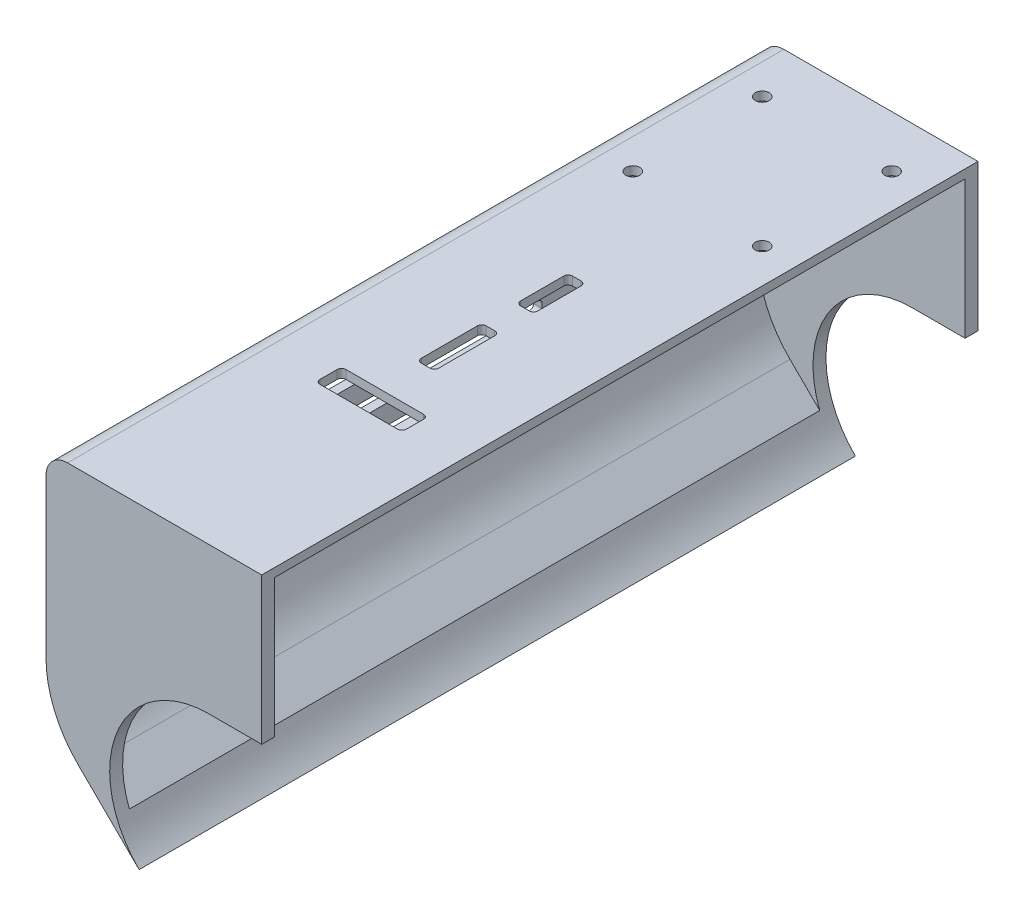
SolidWorks part; units mm, degrees
ref_plane "Front Plane" through (0, 0, 0) normal (0, 0, 1) x (1, 0, 0)
ref_plane "Top Plane" through (0, 0, 0) normal (0, 1, 0) x (1, 0, 0)
ref_plane "Right Plane" through (0, 0, 0) normal (1, 0, 0) x (0, 0, -1)
sketch "Sketch1" plane through (0, 0, 0) normal (0, 0, 1) x (1, 0, 0)
  line L0 (-176.4226, 3.6462) -> (-198.0073, 24.9918)
  line L1 (-198.0073, 24.9918) -> (-198.0073, 77)
  line L2 (-198.0073, 77) -> (-148.0073, 77)
  line L4 (-160.25, 43) -> (-148.0073, 43)
  line L6 (-148.0073, 43) -> (-148.0073, 77)
  arc A1 (-160.25, 43) -> (-176.4226, 3.6462) centre (-160.25, 20) ccw
extrude "Boss-Extrude1" add sketch "Sketch1" against normal blind 3
sketch "Sketch2" plane through (0, 0, -166) normal (0, 0, -1) x (-1, 0, 0)
  line L5 (198.0073, 24.9918) -> (198.0073, 77)
  line L6 (198.0073, 77) -> (148.0073, 77)
  line L7 (148.0073, 77) -> (148.0073, 43)
  line L8 (148.0073, 43) -> (160.25, 43)
  line L9 (176.4226, 3.6462) -> (198.0073, 24.9918)
  line L10 (198.0073, 24.9918) -> (198.0073, 77)
  line L11 (198.0073, 77) -> (148.0073, 77)
  line L12 (148.0073, 77) -> (148.0073, 43)
  line L13 (148.0073, 43) -> (160.25, 43)
  line L14 (176.4226, 3.6462) -> (198.0073, 24.9918)
  arc A1 (176.4226, 3.6462) -> (160.25, 43) centre (160.25, 20) ccw
  arc A2 (176.4226, 3.6462) -> (160.25, 43) centre (160.25, 20) ccw
  dimension "D1" = 0
extrude "Boss-Extrude2" add sketch "Sketch2" against normal blind 3 separate body
sketch "Sketch3" plane through (0, 0, -3) normal (0, 0, -1) x (-1, 0, 0)
  line L0 (181.6864, 11.6645) -> (196.0073, 25.8268)
  line L1 (196.0073, 25.8268) -> (196.0073, 75)
  line L2 (196.0073, 75) -> (148.0073, 75)
  line L3 (148.0073, 77) -> (148.0073, 75)
  line L4 (175.0163, 5.0683) -> (196.0073, 25.8268) construction
  line L5 (198.0073, 24.9918) -> (198.0073, 77)
  line L6 (198.0073, 77) -> (148.0073, 77)
  line L7 (148.0073, 77) -> (148.0073, 43)
  line L8 (148.0073, 43) -> (160.25, 43)
  line L9 (176.4226, 3.6462) -> (198.0073, 24.9918)
  line L10 (198.0073, 24.9918) -> (198.0073, 77)
  line L11 (198.0073, 77) -> (148.0073, 77)
  line L14 (176.4226, 3.6462) -> (198.0073, 24.9918)
  arc A0 (160.25, -3) -> (160.25, 43) centre (160.25, 20) ccw construction
  arc A1 (176.4226, 3.6462) -> (160.25, 43) centre (160.25, 20) ccw
  arc A3 (176.4226, 3.6462) -> (181.6864, 11.6645) centre (160.25, 20) ccw
  dimension "D1" = 0
  dimension "D2" = 2
extrude "Boss-Extrude3" add sketch "Sketch3" along normal up to surface (160 mm away) up to face at (-173.6482, 45.6762, -163)
fillet "Fillet1" radius 5 2 edges at (-198.0073, 77, -83) (-196.0073, 75, -83)
fillet "Fillet2" radius 25 2 edges at (-196.0073, 25.8268, -83) (-198.0073, 24.9918, -83)
sketch "Sketch4" plane through (-198.0073, 0, 0) normal (-1, 0, 0) x (0, 0, 1)
  line L0 (-83, 77) -> (-83, 3.6462) construction
  line L1 (-166, 77) -> (0, 77) construction
  line L2 (-166, 3.6462) -> (0, 3.6462) construction
  line L3 (-112, 59.5) -> (-54, 59.5)
  line L4 (-112, 67) -> (-54, 67)
  line L5 (-113, 66) -> (-113, 65)
  line L6 (-112, 64) -> (-54, 64)
  line L7 (-53, 66) -> (-53, 65)
  line L8 (-113, 58.5) -> (-113, 57.5)
  line L9 (-112, 56.5) -> (-54, 56.5)
  line L10 (-53, 58.5) -> (-53, 57.5)
  line L11 (-112, 52) -> (-54, 52)
  line L12 (-113, 51) -> (-113, 50)
  line L13 (-112, 49) -> (-54, 49)
  line L14 (-53, 51) -> (-53, 50)
  line L15 (-112, 44.5) -> (-54, 44.5)
  line L16 (-113, 43.5) -> (-113, 42.5)
  line L17 (-112, 41.5) -> (-54, 41.5)
  line L18 (-53, 43.5) -> (-53, 42.5)
  arc A0 (-54, 67) -> (-53, 66) centre (-54, 66) cw
  arc A1 (-54, 64) -> (-53, 65) centre (-54, 65) ccw
  arc A2 (-112, 67) -> (-113, 66) centre (-112, 66) ccw
  arc A3 (-113, 65) -> (-112, 64) centre (-112, 65) ccw
  arc A4 (-54, 59.5) -> (-53, 58.5) centre (-54, 58.5) cw
  arc A5 (-54, 56.5) -> (-53, 57.5) centre (-54, 57.5) ccw
  arc A6 (-112, 59.5) -> (-113, 58.5) centre (-112, 58.5) ccw
  arc A7 (-113, 57.5) -> (-112, 56.5) centre (-112, 57.5) ccw
  arc A8 (-54, 52) -> (-53, 51) centre (-54, 51) cw
  arc A9 (-54, 49) -> (-53, 50) centre (-54, 50) ccw
  arc A10 (-112, 52) -> (-113, 51) centre (-112, 51) ccw
  arc A11 (-113, 50) -> (-112, 49) centre (-112, 50) ccw
  arc A12 (-54, 44.5) -> (-53, 43.5) centre (-54, 43.5) cw
  arc A13 (-54, 41.5) -> (-53, 42.5) centre (-54, 42.5) ccw
  arc A14 (-112, 44.5) -> (-113, 43.5) centre (-112, 43.5) ccw
  arc A15 (-113, 42.5) -> (-112, 41.5) centre (-112, 42.5) ccw
  dimension "D1" = 1
  dimension "D2" = 4
extrude "Cut-Extrude1" cut sketch "Sketch4" against normal blind 5
sketch "Sketch5" plane through (0, 77, 0) normal (0, 1, 0) x (1, 0, 0)
  line L0 (-198.0073, 0) -> (-198.0073, 166) construction
  line L1 (-180.5073, 51) -> (-160.5073, 51)
  line L2 (-180.5073, 51) -> (-180.5073, 45)
  line L3 (-180.5073, 45) -> (-160.5073, 45)
  line L4 (-160.5073, 51) -> (-160.5073, 45)
  line L5 (-173.0073, 76) -> (-169.0073, 76)
  line L6 (-173.0073, 76) -> (-173.0073, 61)
  line L7 (-173.0073, 61) -> (-169.0073, 61)
  line L8 (-169.0073, 76) -> (-169.0073, 61)
  line L9 (-173.0073, 96) -> (-169.0073, 96)
  line L10 (-173.0073, 96) -> (-173.0073, 84)
  line L11 (-173.0073, 84) -> (-169.0073, 84)
  line L12 (-169.0073, 96) -> (-169.0073, 84)
  line L13 (-148.0073, 0) -> (-193.0073, 0) construction
  line L14 (-170.5073, 0) -> (-170.5073, 45) construction
  dimension "D1" = 6
  dimension "D2" = 20
  dimension "D3" = 10
  dimension "D4" = 45
  dimension "D5" = 25
  dimension "D6" = 4
  dimension "D7" = 15
  dimension "D8" = 10
  dimension "D9" = 4
  dimension "D10" = 12
  dimension "D11" = 8
  dimension "D12" = 0
extrude "Cut-Extrude2" cut sketch "Sketch5" against normal blind 2
sketch "Sketch6" plane through (0, 77, 0) normal (0, 1, 0) x (1, 0, 0)
  circle A0 centre (-156.0073, 154) radius 1.6
  circle A1 centre (-156.0073, 124) radius 1.6
  circle A2 centre (-186.0073, 124) radius 1.6
  circle A3 centre (-186.0073, 154) radius 1.6
extrude "Cut-Extrude3" cut sketch "Sketch6" against normal up to surface (2 mm away) up to face at (-170.5073, 75, -48)
fillet "Fillet3" radius 1 12 edges at (-169.0073, 76, -76) (-173.0073, 76, -76) (-169.0073, 76, -84) (-173.0073, 76, -84) (-173.0073, 76, -96) (-169.0073, 76, -96) (-160.5073, 76, -45) (-160.5073, 76, -51) (-180.5073, 76, -51) (-180.5073, 76, -45) (-173.0073, 76, -61) (-169.0073, 76, -61)
